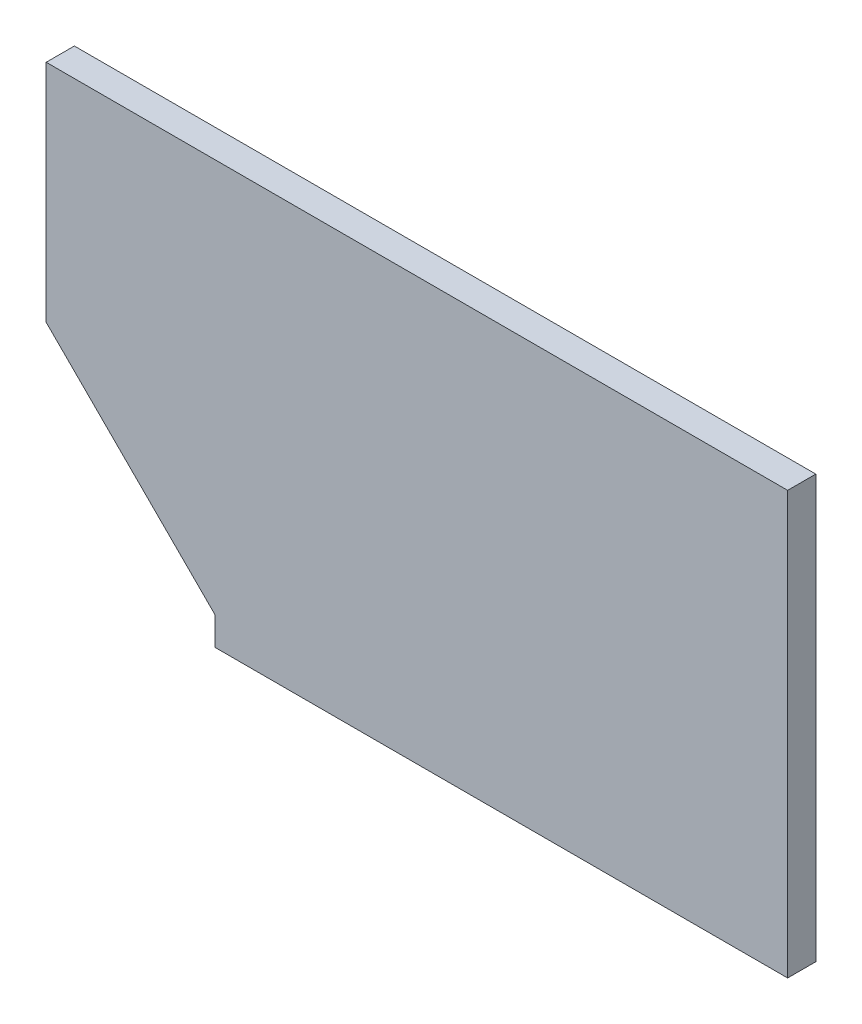
SolidWorks part; units mm, degrees
ref_plane "Front Plane" through (0, 0, 0) normal (0, 0, 1) x (1, 0, 0)
ref_plane "Top Plane" through (0, 0, 0) normal (0, 1, 0) x (1, 0, 0)
ref_plane "Right Plane" through (0, 0, 0) normal (1, 0, 0) x (0, 0, -1)
sketch "Sketch1" plane through (0, 0, 0) normal (0, 0, 1) x (1, 0, 0)
  line L0 (0, 0) -> (0, -45)
  line L1 (0, -45) -> (-61, -45)
  line L2 (-61, -45) -> (-61, -42)
  line L3 (-61, -42) -> (-79, -24)
  line L4 (-79, -24) -> (-79, 0)
  line L8 (-79, 0) -> (0, 0)
  dimension "D1" = 61
  dimension "D2" = 18
  dimension "D3" = 3
  dimension "D4" = 45
  dimension "D5" = 45
extrude "Boss-Extrude1" add sketch "Sketch1" against normal blind 3
